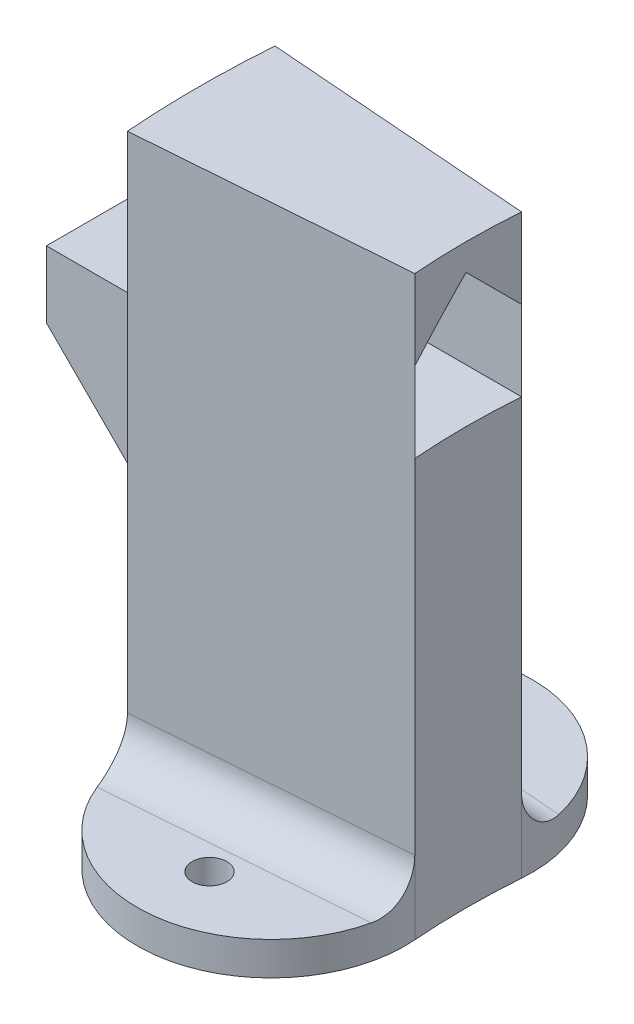
SolidWorks part; units mm, degrees
ref_plane "Front Plane" through (0, 0, 0) normal (0, 0, 1) x (1, 0, 0)
ref_plane "Top Plane" through (0, 0, 0) normal (0, 1, 0) x (1, 0, 0)
ref_plane "Right Plane" through (0, 0, 0) normal (1, 0, 0) x (0, 0, -1)
sketch "Sketch1" plane through (0, 0, 0) normal (0, 1, 0) x (1, 0, 0)
  line L0 (-158.3624, 12.1009) -> (-156.4215, 37.5009) construction
  line L9 (-158.3624, -12.1009) -> (-156.4215, -37.5009) construction
  line L10 (-183.7624, -14.0418) -> (-132.9624, -10.16)
  line L11 (-183.7624, 14.0418) -> (-132.9624, 10.16)
  arc A0 (-132.9624, 10.16) -> (-132.9624, -10.16) centre (0, 0) ccw
  arc A1 (-183.7624, 14.0418) -> (-183.7624, -14.0418) centre (0, 0) ccw
  arc A2 (-132.9624, 10.16) -> (-183.7624, 14.0418) centre (-158.3624, 12.1009) ccw
  arc A3 (-183.7624, -14.0418) -> (-132.9624, -10.16) centre (-158.3624, -12.1009) ccw
  circle A4 centre (-157.3919, -24.8009) radius 3.325
  circle A5 centre (-157.3919, 24.8009) radius 3.325
  point P0 (-133.35, 0)
  dimension "D1" = 133.35
  dimension "D3" = 50.8
  dimension "D4" = 6.65
  dimension "D2" = 20.32
extrude "Boss-Extrude1" add sketch "Sketch1" along normal blind 79.3362 contours L11 A1 L10 A0 region at (-160.0308, 0, 0)
extrude "Boss-Extrude2" add sketch "Sketch1<6>" along normal blind 6.35 contours L10 A3 | L11 A2 region at (-158.3184, 0, 12.6771) region at (-156.4655, 0, -36.9247)
sketch "Sketch1<6>" plane through (0, 0, 0) normal (0, 1, 0) x (1, 0, 0) same geometry as "Sketch1"
fillet "Fillet1" radius 7.62 2 edges at (-158.3624, 6.35, -12.1009) (-158.3624, 6.35, 12.1009)
sketch "Sketch2" plane through (0, 79.3362, 0) normal (0, 1, 0) x (1, 0, 0)
  line L0 (-183.7624, -14.0418) -> (-132.9624, -10.16) construction
  line L1 (-183.7624, 14.0418) -> (-132.9624, 10.16) construction
  line L2 (-183.7624, -14.0418) -> (-132.9624, -10.16)
  line L3 (-183.7624, 14.0418) -> (-132.9624, 10.16)
  line L4 (-132.9624, -10.16) -> (-184.0178, -10.16)
  line L5 (-132.9624, 10.16) -> (-184.0178, 10.16)
  arc A0 (-183.7624, 14.0418) -> (-183.7624, -14.0418) centre (0, 0) ccw construction
  arc A1 (-183.7624, 14.0418) -> (-184.0178, 10.16) centre (0, 0) ccw
  arc A2 (-184.0178, -10.16) -> (-183.7624, -14.0418) centre (0, 0) ccw
extrude "Boss-Extrude3" add sketch "Sketch2" along normal blind 27.94
sketch "Sketch3" plane through (0, 107.2762, 0) normal (0, 1, 0) x (1, 0, 0)
  line L1 (-183.7624, -14.0418) -> (-132.9624, -10.16) construction
  line L2 (-132.9624, 10.16) -> (-183.7624, 14.0418)
  line L3 (-183.7624, -14.0418) -> (-132.9624, -10.16)
  line L4 (-132.9624, 10.16) -> (-183.7624, 14.0418) construction
  arc A0 (-183.7624, 14.0418) -> (-184.0178, 10.16) centre (0, 0) ccw construction
  arc A1 (-183.7624, 14.0418) -> (-183.7624, -14.0418) centre (0, 0) ccw
  arc A2 (-132.9624, 10.16) -> (-132.9624, -10.16) centre (0, 0) ccw
  arc A3 (-184.0178, 10.16) -> (-184.0178, -10.16) centre (0, 0) ccw construction
  arc A4 (-132.9624, 10.16) -> (-132.9624, -10.16) centre (0, 0) ccw construction
extrude "Boss-Extrude4" add sketch "Sketch3" along normal blind 2.54
chamfer "Chamfer1" distance 12.7 angle 45 2 edges at (-158.4901, 107.2762, -10.16) (-158.4901, 107.2762, 10.16)
sketch "Sketch4" plane through (0, 79.3362, 0) normal (0, 1, 0) x (1, 0, 0)
  line L0 (-184.0178, 10.16) -> (-203.0678, 10.16)
  line L1 (-184.0178, -10.16) -> (-203.0678, -10.16)
  line L2 (-203.0678, 10.16) -> (-203.0678, -10.16)
  arc A0 (-183.7624, 14.0418) -> (-183.7624, -14.0418) centre (0, 0) ccw construction
  arc A1 (-184.0178, 10.16) -> (-184.0178, -10.16) centre (0, 0) ccw
  dimension "D1" = 19.05
extrude "Boss-Extrude5" add sketch "Sketch4" against normal blind 50.8 separate body
chamfer "Chamfer2" distance 38.1 angle 45 1 edges at (-203.0678, 28.5362, 0)
sketch "Sketch5" plane through (0, 79.3362, 0) normal (0, 1, 0) x (1, 0, 0)
  line L1 (-203.0678, 10.16) -> (-203.0678, -10.16) construction
  circle A0 centre (-192.9078, 0) radius 2.9908
  point P4 (-203.0678, 0)
  dimension "D1" = 10.16
  dimension "D2" = 5.9817
extrude "Cut-Extrude1" cut sketch "Sketch5" against normal blind 10.16
equation "\"1.5inin\"=2"
